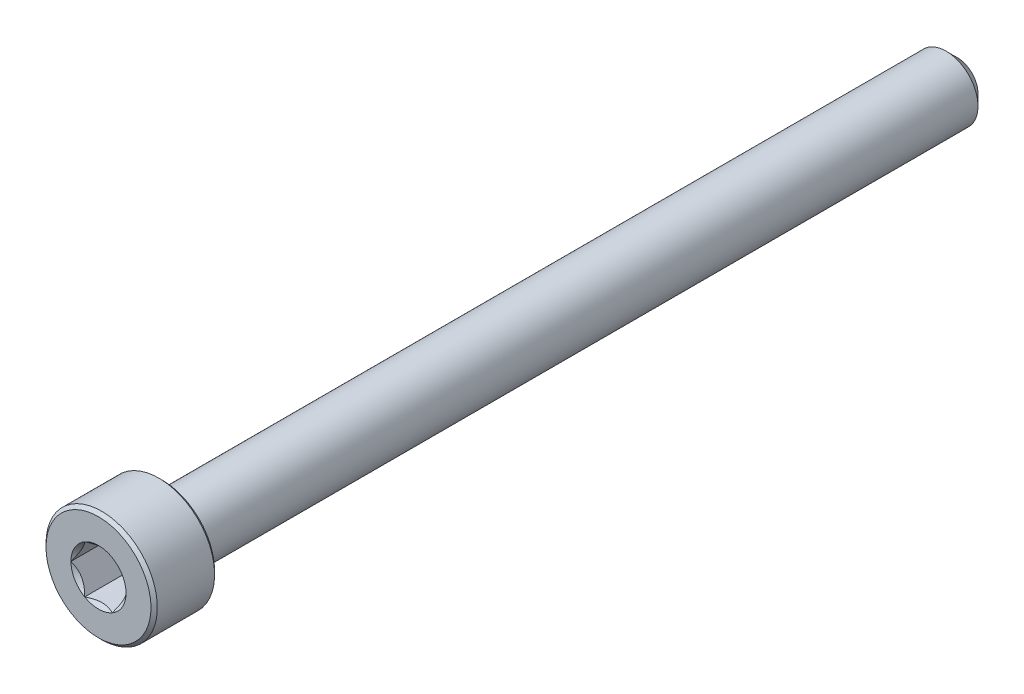
SolidWorks part; units mm, degrees
material "Plain Carbon Steel"
ref_plane "Front Plane" through (0, 0, 0) normal (0, 0, 1) x (1, 0, 0)
ref_plane "Top Plane" through (0, 0, 0) normal (0, 1, 0) x (1, 0, 0)
ref_plane "Right Plane" through (0, 0, 0) normal (1, 0, 0) x (0, 0, -1)
sketch "Sketch1" plane through (0, 0, 0) normal (1, 0, 0) x (0, 0, -1)
  line L0 (-27, 0) -> (27, 0) construction
  line L1 (27, 0) -> (27, 1.3) construction
  line L2 (27, 1.3) -> (26.3, 2) construction
  line L3 (26.3, 2) -> (7, 2) construction
  line L4 (7, 2) -> (-23, 2) construction
  line L5 (-23, 2) -> (-23, 3.5) construction
  line L6 (-23, 3.5) -> (-27, 3.5) construction
  line L7 (-27, 3.5) -> (-27, 0) construction
  line L8 (27, 1.3) -> (27, 2) construction
  line L9 (26.9563, 2.0758) -> (27.3063, 1.4696) construction
  line L10 (27.3063, 1.4696) -> (27.6562, 2.0758) construction
  line L11 (27.6562, 2.0758) -> (26.9563, 2.0758) construction
  line L12 (27.3063, 2.0758) -> (27.3063, 2) construction
  line L13 (27.3063, 1.4696) -> (27.3063, 1.5453) construction
  line L14 (27.2625, 1.5453) -> (27.35, 1.5453) construction
  line L15 (27, 2) -> (27.6125, 2) construction
  line L16 (26.9781, 2.0379) -> (27.6344, 2.0379) construction
  line L17 (27, 0) -> (27, -2) construction
  line L18 (-23.2, 3.5) -> (-23, 3.3) construction
  line L19 (-26.8, 3.5) -> (-27, 3.3) construction
  point P0 (-27, 1.5)
  point P3 (24.55, 2)
  point P4 (0, 0)
  point P18 (6, 2)
  point P22 (27.3063, 1.5453)
  point P24 (7, 2)
  point P25 (27.3063, 2)
  point P28 (27.3063, 2.0379)
  point P29 (24.55, -2)
  point P30 (-22, 2)
  point P31 (-25, 3.5)
  point P37 (-23.7, 3.5)
  point P38 (-26.7, 3.5)
  dimension "head height" = 4
  dimension "threaded length" = 20
  dimension "D1" = 45
  dimension "head dia" = 7
  dimension "thread dia" = 4
  dimension "drive size" = 3
  dimension "pitch" = 0.7
  dimension "D2" = 0.0875
  dimension "D3" = 0.7
  dimension "D4" = 2.45
  dimension "D5" = 1
  dimension "D6" = 1
  dimension "D7" = 0.2
  dimension "D8" = 0.2
  dimension "D9" = 0.2
  dimension "D10" = 0.1
  dimension "D11" = 0.5
  dimension "length" = 50
sketch "Sketch2" plane through (0, 0, 0) normal (1, 0, 0) x (0, 0, -1)
  line L0 (-27, 0) -> (-27, 3.3)
  line L1 (-26.8, 3.5) -> (-23.2, 3.5)
  line L2 (-23, 3.3) -> (-23, 2)
  line L3 (-23, 2) -> (26.3, 2)
  line L4 (26.3, 2) -> (27, 1.3)
  line L5 (27, 1.3) -> (27, 0)
  line L6 (-23.2, 3.5) -> (-23, 3.3) construction
  line L7 (27, 0) -> (-27, 0)
  line L8 (-26.8, 3.5) -> (-27, 3.3) construction
  line L9 (-23.2, 3.5) -> (-23, 3.3)
  line L10 (-26.8, 3.5) -> (-27, 3.3)
revolve "Revolve1" add sketch "Sketch2" angle 360 about L7
sketch "Sketch3" plane through (0, 0, 27) normal (0, 0, 1) x (1, 0, 0)
  line L1 (0.866, 1.5) -> (-0.866, 1.5)
  line L2 (-0.866, 1.5) -> (-1.7321, 0)
  line L3 (-1.7321, 0) -> (-0.866, -1.5)
  line L4 (-0.866, -1.5) -> (0.866, -1.5)
  line L5 (0.866, -1.5) -> (1.7321, 0)
  line L6 (1.7321, 0) -> (0.866, 1.5)
  circle A0 centre (0, 0) radius 1.5 construction
extrude "Cut-Extrude1" cut sketch "Sketch3" against normal offset from surface (3 mm away) 1 up to face at (-3.3, 0, 23)
sketch "Sketch4" plane through (0, 0, 27) normal (0, 0, 1) x (1, 0, 0)
  circle A0 centre (0, 0) radius 1.7321
extrude "Cut-Extrude2" cut sketch "Sketch4" against normal up to vertex (2 mm away) draft 45 up to point (0, 3.5, 25)
ref_plane "Plane1" [suppressed] through (0, 0, -7) normal (0, 0, 1) x (1, 0, 0)
split "Split1" [suppressed] bodies to split 106
sketch "Sketch6" [suppressed] plane through (0, 0, -27) normal (0, 0, -1) x (-1, 0, 0)
  circle A0 centre (0, 0) radius 2
curve "Helix/Spiral1" [suppressed] pitch 0.7 height 20.7 turns 29.5714
sketch "Sketch7" [suppressed] plane through (0, 0, 0) normal (1, 0, 0) x (0, 0, -1)
  line L0 (26.9781, 2.0379) -> (27.6344, 2.0379)
  line L1 (27.6344, 2.0379) -> (27.35, 1.5453)
  line L2 (27.35, 1.5453) -> (27.2625, 1.5453)
  line L3 (27.2625, 1.5453) -> (26.9781, 2.0379)
sweep "Cut-Sweep1" [suppressed] cut profiles "Sketch7" path "Helix/Spiral1"
sketch "Sketch8" [suppressed] plane through (0, 0, -7) normal (0, 0, -1) x (-1, 0, 0)
  circle A0 centre (0, 0) radius 2
extrude "Boss-Extrude1" [suppressed] add sketch "Sketch8" along normal through all draft 45
ref_plane "Plane2" [suppressed] through (0, 0, 25) normal (0, 0, 1) x (1, 0, 0)
sketch "Sketch9" [suppressed] plane through (0, 0, 25) normal (0, 0, 1) x (1, 0, 0)
  line L0 (0, 3.325) -> (0.0611, 3.4995)
  line L1 (0, 3.325) -> (-0.0611, 3.4995)
  line L2 (0, 3.5) -> (0, 0) construction
  line L3 (-0.0611, 3.4995) -> (0, 0) construction
  line L4 (0, 0) -> (0.0611, 3.4995) construction
  arc A0 (0.0611, 3.4995) -> (-0.0611, 3.4995) centre (0, 0) ccw
  circle A1 centre (0, 0) radius 3.325 construction
  dimension "D2" = 6.65
  dimension "D3" = 2
extrude "Cut-Extrude4" [suppressed] cut sketch "Sketch9" against normal up to vertex and the other way up to vertex
pattern_circular "CirPattern2" [suppressed] count 175 over 360 about axis through (0, 0, 27) along (0, 0, -1) of bodies 113
equation "\"D2@Sketch1\"=\"pitch@Sketch1\"/8"
equation "\"D3@Sketch1\"=\"pitch@Sketch1\""
equation "\"D3@Helix/Spiral1\"=\"threaded length@Sketch1\"+\"pitch@Sketch1\""
equation "\"D4@Helix/Spiral1\"=\"pitch@Sketch1\""
equation "\"D4@Sketch1\"=\"pitch@Sketch1\"*3.5"
equation "\"D7@Sketch1\"=\"head height@Sketch1\"*.05"
equation "\"D8@Sketch1\"=\"D7@Sketch1\""
equation "\"D9@Sketch1\"=\"D7@Sketch1\""
equation "\"D10@Sketch1\"=\"D7@Sketch1\"/2"
equation "\"D11@Sketch1\"=\"D10@Sketch1\"*5"
equation "\"D2@Sketch9\"=\"D1@Sketch9\"*.95"
equation "\"D1@CirPattern2\"= ( 360 / \"D3@Sketch9\" ) - 5"
